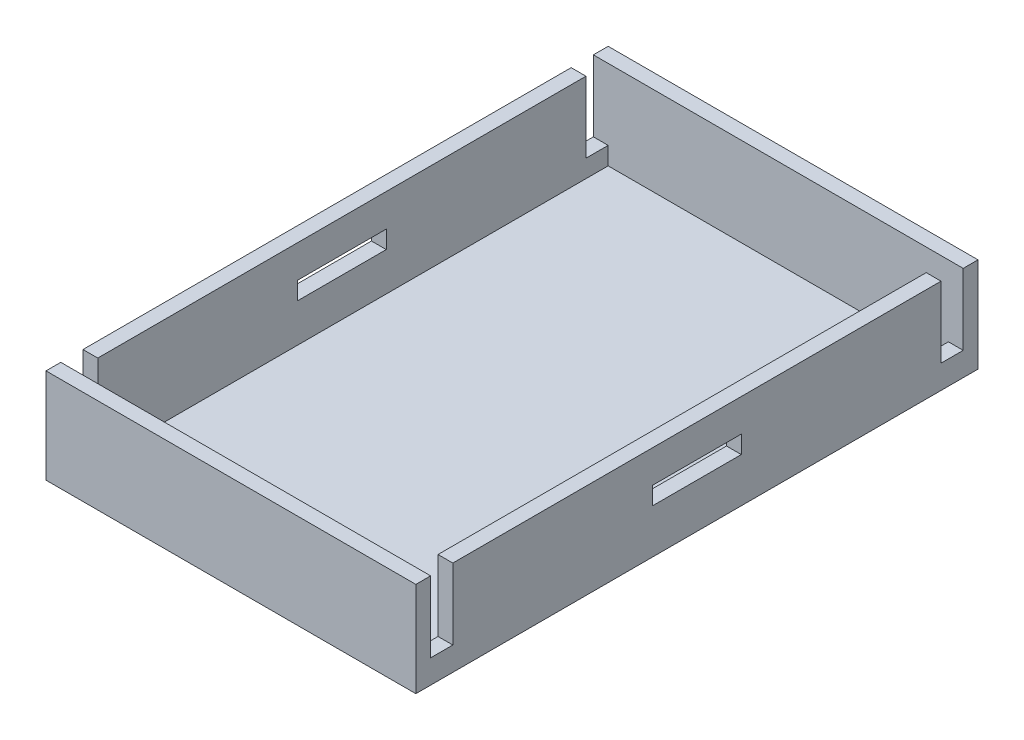
SolidWorks part; units mm, degrees
ref_plane "Front Plane" through (0, 0, 0) normal (0, 0, 1) x (1, 0, 0)
ref_plane "Top Plane" through (0, 0, 0) normal (0, 1, 0) x (1, 0, 0)
ref_plane "Right Plane" through (0, 0, 0) normal (1, 0, 0) x (0, 0, -1)
sketch "Sketch1" plane through (0, 0, 0) normal (0, 1, 0) x (1, 0, 0)
  line L1 (-12.5, -19) -> (12.5, -19)
  line L2 (-12.5, -19) -> (-12.5, 19)
  line L3 (-12.5, 19) -> (12.5, 19)
  line L4 (12.5, -19) -> (12.5, 19)
  line L5 (-12.5, -19) -> (12.5, 19) construction
  line L6 (-12.5, 19) -> (12.5, -19) construction
  point P0 (0, 0)
  dimension "D1" = 25
  dimension "D2" = 38
extrude "Boss-Extrude1" add sketch "Sketch1" along normal blind 6.4
sketch "Sketch2" plane through (0, 6.4, 0) normal (0, 1, 0) x (1, 0, 0)
  line L0 (-12.5, 19) -> (-12.5, -19) construction
  line L1 (-11.5, -18) -> (11.5, -18)
  line L2 (-11.5, -18) -> (-11.5, 18)
  line L3 (-11.5, 18) -> (11.5, 18)
  line L4 (11.5, -18) -> (11.5, 18)
  line L5 (-11.5, -18) -> (11.5, 18) construction
  line L6 (-11.5, 18) -> (11.5, -18) construction
  line L7 (-11.5, 18) -> (-12.5, 18)
  line L8 (-11.5, 18) -> (-11.5, 16.5)
  line L9 (-11.5, 16.5) -> (-12.5, 16.5)
  line L10 (-12.5, 18) -> (-12.5, 16.5)
  line L11 (0, -55) -> (0, 55) construction
  line L12 (11.5, 16.5) -> (12.5, 16.5)
  line L13 (12.5, 18) -> (12.5, 16.5)
  line L14 (11.5, 18) -> (12.5, 18)
  line L15 (-55, 0) -> (55, 0) construction
  line L16 (11.5, -16.5) -> (12.5, -16.5)
  line L17 (12.5, -18) -> (12.5, -16.5)
  line L18 (11.5, -18) -> (12.5, -18)
  line L19 (-11.5, -16.5) -> (-12.5, -16.5)
  line L20 (-12.5, -18) -> (-12.5, -16.5)
  line L21 (-11.5, -18) -> (-12.5, -18)
  point P0 (0, 0)
  line M5 (12.5, -19) -> (12.5, 19)
  line M7 (-12.5, 19) -> (-12.5, -19)
  dimension "D1" = 23
  dimension "D2" = 36
  dimension "D3" = 1.5
extrude "Cut-Extrude1" cut sketch "Sketch2" against normal blind 6 contours L1 L4 L3 L2 region at (0, 6.4, 0)
extrude "Cut-Extrude2" cut sketch "Sketch2<3>" against normal blind 4.8 contours L9 L2 L7 M7 | L14 L4 L12 M5 | L21 L2 L19 M7 | L4 L18 L16 M5 region at (-12, 6.4, 17.25) region at (12, 6.4, 17.25) region at (-12, 6.4, -17.25) region at (12, 6.4, -17.25)
sketch "Sketch2<3>" plane through (0, 6.4, 0) normal (0, 1, 0) x (1, 0, 0) same geometry as "Sketch2"
sketch "Sketch3" plane through (0, 0, 0) normal (1, 0, 0) x (0, 0, -1)
  line L0 (0, 0) -> (0, 6.4) construction
  line L1 (-16.5, 6.4) -> (16.5, 6.4) construction
  line L2 (-19, 0) -> (19, 0) construction
  line L3 (-3, 3) -> (3, 3)
  line L4 (-3, 3) -> (-3, 4.2)
  line L5 (-3, 4.2) -> (3, 4.2)
  line L6 (3, 3) -> (3, 4.2)
  line L7 (-3, 3) -> (3, 4.2) construction
  line L8 (-3, 4.2) -> (3, 3) construction
  point P5 (0, 3.6)
  dimension "D1" = 6
  dimension "D2" = 1.2
  dimension "D3" = 3
extrude "Cut-Extrude3" cut sketch "Sketch3" against normal through all both and the other way through all
